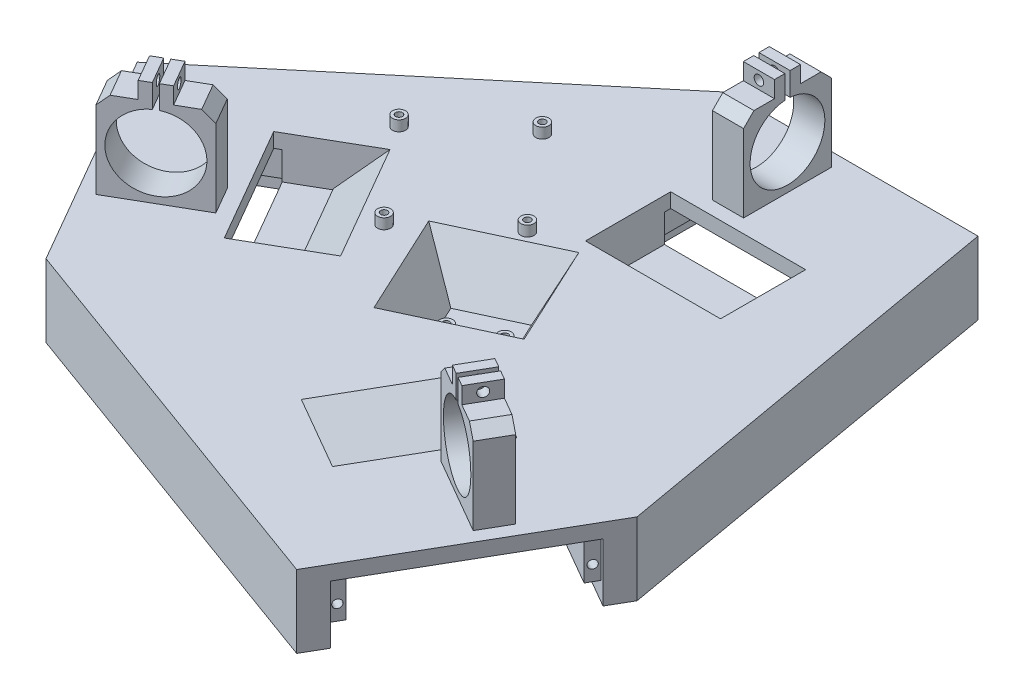
SolidWorks part; units mm, degrees
note: '?' marks a value the reader was unsure of.
ref_plane "Front Plane" through (0, 0, 0) normal (0, 0, 1) x (1, 0, 0)
ref_plane "Top Plane" through (0, 0, 0) normal (0, 1, 0) x (1, 0, 0)
ref_plane "Right Plane" through (0, 0, 0) normal (1, 0, 0) x (0, 0, -1)
sketch "Sketch1" plane through (0, 0, 0) normal (0, 1, 0) x (1, 0, 0)
  line L3 (-125, -72.1688) -> (0, 0)
  line L4 (0, 0) -> (125, -72.1688)
  line L5 (0, 144.3376) -> (0, 0)
  line L6 (-20, 144.3376) -> (100, 144.3376)
  line L7 (135, -54.8483) -> (75, -158.7713)
  line L8 (-175, 14.4338) -> (-115, -89.4893)
  line L9 (-175, 14.4338) -> (-20, 144.3376)
  line L10 (100, 144.3376) -> (135, -54.8483)
  line L11 (75, -158.7713) -> (-115, -89.4893)
  line L12 (0, 0) -> (129.9038, -75) construction
  dimension "D1" = 250
  dimension "D2" = 120
  dimension "D3" = 120
  dimension "D4" = 120
  dimension "D5" = 100
  dimension "D6" = 100
  dimension "D7" = 100
extrude "Boss-Extrude1" add sketch "Sketch1" along normal blind 35
ref_axis "Central Axis" through (0, -4.265, 0) along (0, 1, 0)?
ref_plane "Mechanism Arm Plane" through (0, 0, 0) normal (1, 0, 0) x (0, 0, -1)
ref_plane "Mech Arm Plane 2" through (0, 0, 0) normal (0.5, 0, 0.866) x (0, 1, 0)
ref_plane "Mech Arm Plane 3" through (0, 0, 0) normal (0.5, 0, -0.866) x (0, 1, 0)
ref_plane "Camera Plane" through (0, 10, 0) normal (0, 1, 0) x (1, 0, 0)
sketch "Sketch16" plane through (0, 10, 0) normal (0, 1, 0) x (1, 0, 0)
  line L0 (-7.5666, -8.8618) -> (-16.5148, 10.3572)
  line L1 (-7.5666, -8.8618) -> (11.6524, 0.0863)
  line L2 (-16.5148, 10.3572) -> (2.7043, 19.3053)
  line L3 (11.6524, 0.0863) -> (2.7043, 19.3053)
  line L4 (-7.5666, -8.8618) -> (2.7043, 19.3053) construction
  line L5 (-16.5148, 10.3572) -> (11.6524, 0.0863) construction
  line L6 (-21.8293, 12.2952) -> (4.6422, 24.6199)
  line L7 (16.9669, -1.8516) -> (4.6422, 24.6199)
  line L8 (-9.5046, -14.1764) -> (16.9669, -1.8516)
  line L9 (-9.5046, -14.1764) -> (-21.8293, 12.2952)
  point P1 (-2.4312, 5.2218)
  dimension "D1" = 4
  dimension "D2" = 21.2
sketch "Sketch2" plane through (0, 0, -144.3376) normal (0, 0, -1) x (-1, 0, 0)
  line L0 (-75, 0) -> (115, 0) construction
  line L1 (-88, 0) -> (8, 0)
  line L2 (-88, 0) -> (-88, 28)
  line L3 (-88, 28) -> (8, 28)
  line L4 (8, 0) -> (8, 28)
  line L5 (-40, 28) -> (-40, 0) construction
  line L6 (20, 35) -> (20, 0) construction
  line L7 (-100, 35) -> (-100, 0) construction
  dimension "D1" = 28
  dimension "D2" = 96
extrude "Cut-Extrude1" cut sketch "Sketch2" against normal blind 2.5
sketch "Sketch3" plane through (0, 0, -141.8376) normal (0, 0, -1) x (-1, 0, 0)
  line L0 (8, 0) -> (8, 28) construction
  line L1 (-88, 0) -> (8, 0)
  line L2 (-88, 0) -> (-88, 9)
  line L3 (-88, 9) -> (8, 9)
  line L4 (8, 0) -> (8, 9)
  line L5 (8, 28) -> (-88, 28) construction
  line L6 (-82, 9) -> (2, 9)
  line L7 (-82, 9) -> (-82, 28)
  line L8 (-82, 28) -> (2, 28)
  line L9 (2, 9) -> (2, 28)
  line L10 (-40, 28) -> (-40, 9) construction
  line L11 (-88, 28) -> (-88, 0) construction
  line M6 (-88, 28) -> (-88, 0)
  line M7 (-88, 0) -> (8, 0)
  line M8 (8, 0) -> (8, 28)
  line M9 (8, 28) -> (-88, 28)
  dimension "D1" = 9
  dimension "D2" = 84
extrude "Cut-Extrude2" cut sketch "Sketch3" against normal blind 56 contours L10 L8 L7 L3 | L10 L6 L9 M9 | L3 L6 M6 M7 M8
sketch "Sketch4" plane through (0, 0, -141.8376) normal (0, 0, -1) x (-1, 0, 0)
  line L0 (-85, 9) -> (-85, 28) construction
  line L1 (-88, 9) -> (-82, 9) construction
  line L2 (8, 28) -> (-88, 28) construction
  line L3 (5, 9) -> (5, 28) construction
  line L4 (2, 9) -> (8, 9) construction
  circle A0 centre (-85, 16.25) radius 2
  circle A1 centre (5, 16.25) radius 2
  dimension "D1" = 4
  dimension "D2" = 7.25
extrude "Cut-Extrude3" cut sketch "Sketch4" against normal blind 6
sketch "Sketch5" plane through (0, 0, -85.8376) normal (0, 0, -1) x (-1, 0, 0)
  line L0 (-40, 36.5) -> (-40, 14.5) construction
  line L1 (-72.5, 14.5) -> (-7.5, 14.5)
  line L2 (-72.5, 14.5) -> (-72.5, 36.5)
  line L3 (-72.5, 36.5) -> (-7.5, 36.5)
  line L4 (-7.5, 14.5) -> (-7.5, 36.5)
  line L5 (2, 9) -> (2, 28) construction
  line L6 (-82, 9) -> (-82, 28) construction
  line L7 (2, 9) -> (8, 9) construction
  dimension "D1" = 22
  dimension "D2" = 65
  dimension "D3" = 5.5
extrude "Cut-Extrude4" cut sketch "Sketch5" against normal blind 18 and the other way blind 3
chamfer "Chamfer2" distance 20 angle 45 1 edges at (40, 35, -67.8376)
ref_plane "Plane2" through (36, 0, 0) normal (1, 0, 0) x (0, 0, -1)
sketch "Sketch7" plane through (36, 0, 0) normal (1, 0, 0) x (0, 0, -1)
  line L0 (144.3376, 35) -> (-54.8483, 35) construction
  line L1 (95.4376, 35) -> (137.7376, 35)
  line L2 (95.4376, 35) -> (95.4376, 72.3)
  line L3 (100.4376, 77.3) -> (115.3376, 77.3)
  line L4 (137.7376, 35) -> (137.7376, 72.3)
  line L5 (144.3376, 35) -> (144.3376, 0) construction
  line L6 (95.4376, 72.3) -> (100.4376, 77.3)
  line L7 (132.7376, 77.3) -> (137.7376, 72.3)
  line L8 (95.4376, 56.15) -> (137.7376, 56.15) construction
  line L9 (116.5876, 56.15) -> (116.5876, 35) construction
  line L10 (115.3376, 77.3) -> (115.3376, 74.1065)
  line L11 (117.8376, 77.3) -> (117.8376, 74.1065)
  line L12 (117.8376, 77.3) -> (132.7376, 77.3)
  line L13 (115.3376, 77.3) -> (115.3376, 85.3)
  line L14 (115.3376, 85.3) -> (110.3376, 85.3)
  line L15 (110.3376, 85.3) -> (110.3376, 77.3)
  line L16 (117.8376, 77.3) -> (117.8376, 85.3)
  line L17 (117.8376, 85.3) -> (122.8376, 85.3)
  line L18 (122.8376, 85.3) -> (122.8376, 77.3)
  arc A0 (115.3376, 74.1065) -> (117.8376, 74.1065) centre (116.5876, 56.15) ccw
  point P1 (137.7376, 77.3)
  point P2 (95.4376, 77.3)
  point P22 (116.5876, 35)
  dimension "D4" = 36
  dimension "D1" = 42.3
  dimension "D2" = 6.6
  dimension "D3" = 42.3
  dimension "D5" = 2.5
  dimension "D8" = 5
  dimension "D9" = 8
extrude "Boss-Extrude4" add sketch "Sketch7" against normal blind 15 contours L14 L15 L3 L13 | L18 L17 L16 L12
sketch "Sketch10" plane through (0, 0, -122.8376) normal (0, 0, -1) x (-1, 0, 0)
  line L0 (-36, 81.3) -> (-21, 81.3) construction
  line L1 (-36, 85.3) -> (-36, 77.3) construction
  line L2 (-21, 85.3) -> (-21, 77.3) construction
  line L3 (-28.5, 85.3) -> (-28.5, 77.3) construction
  line L4 (-21, 85.3) -> (-36, 85.3) construction
  line L5 (-21, 77.3) -> (-36, 77.3) construction
  circle A0 centre (-28.5, 81.3) radius 2.3
  dimension "D1" = 4.6
extrude "Cut-Extrude5" cut sketch "Sketch10" against normal up to surface (12.5 mm away) up to face at (28.5, 81.3, -110.3376)
pattern_circular "Motor/Driver Patterned" count 3 over 360 about axis through (0, 0, 0) along (0, 1, 0) of "Cut-Extrude4", "Cut-Extrude3", "Cut-Extrude2", "Cut-Extrude1", "Cut-Extrude5", "Boss-Extrude4", "Chamfer2"
extrude "Cut-Extrude6" cut sketch "Sketch16" along normal up to surface (25 mm away) draft 26.75 contours L9 L8 L7 L6 L3 L1 L0 L2 | L1 L3 L2 L0
sketch "Sketch11" plane through (0, 35, 0) normal (0, 1, 0) x (1, 0, 0)
  line L0 (-85.1107, 50.6262) -> (-47.5559, 82.1005) construction
  line L1 (-85.1107, 50.6262) -> (-47.8554, 6.1735) construction
  line L2 (-47.5559, 82.1005) -> (-10.3006, 37.6479) construction
  line L3 (-47.8554, 6.1735) -> (-10.3006, 37.6479) construction
  line L4 (-47.5559, 82.1005) -> (-47.8554, 6.1735) construction
  line L5 (-175, 14.4338) -> (-20, 144.3376) construction
  circle A0 centre (-10.3006, 37.6479) radius 1.65
  circle A1 centre (-47.8554, 6.1735) radius 1.65
  circle A2 centre (-85.1107, 50.6262) radius 1.65
  circle A3 centre (-47.5559, 82.1005) radius 1.65
  circle A4 centre (-10.3006, 37.6479) radius 3.15
  circle A5 centre (-47.5559, 82.1005) radius 3.15
  circle A6 centre (-85.1107, 50.6262) radius 3.15
  circle A7 centre (-47.8554, 6.1735) radius 3.15
  dimension "D3" = 3.3
  dimension "D1" = 58
  dimension "D2" = 49
  dimension "D5" = 30
  dimension "D4" = 1.5
extrude "RaspberryPi5 Standoff" add sketch "Sketch11" along normal blind 5
sketch "Sketch13" plane through (0, 10, 0) normal (0, 1, 0) x (1, 0, 0)
  line L0 (-7.5666, -8.8618) -> (-11.6524, -0.0863) construction
  line L1 (-7.5666, -8.8618) -> (11.6524, 0.0863) construction
  line L2 (-11.6524, -0.0863) -> (7.5666, 8.8618) construction
  line L3 (11.6524, 0.0863) -> (7.5666, 8.8618) construction
  line L4 (-7.5666, -8.8618) -> (7.5666, 8.8618) construction
  line L5 (-11.6524, -0.0863) -> (11.6524, 0.0863) construction
  line L6 (-47.8554, 6.1735) -> (-10.3006, 37.6479) construction
  circle A0 centre (-11.6524, -0.0863) radius 1.65
  circle A1 centre (7.5666, 8.8618) radius 1.65
  circle A2 centre (11.6524, 0.0863) radius 1.65
  circle A3 centre (-7.5666, -8.8618) radius 1.65
  circle A4 centre (-10.3006, 37.6479) radius 1.65 construction
  circle A5 centre (7.5666, 8.8618) radius 3.15
  circle A6 centre (-11.6524, -0.0863) radius 3.15
  circle A7 centre (-7.5666, -8.8618) radius 3.15
  circle A8 centre (11.6524, 0.0863) radius 3.15
  circle A9 centre (-10.3006, 37.6479) radius 3.15 construction
  point P1 (0, 0)
  dimension "D1" = 9.68
  dimension "D2" = 21.2
  dimension "D3" = 15
extrude "Boss-Extrude6" add sketch "Sketch13" along normal blind 5
sketch "Sketch12" [suppressed] plane through (0, 35, 0) normal (0, 1, 0) x (1, 0, 0)
  line L0 (0, 0) -> (-35.4629, 28.8743)
  line L2 (0, 0) -> (-7.2744, -45.1489)
  line L3 (75, -158.7713) -> (-115, -89.4893) construction
  line L4 (-35.4629, 28.8743) -> (-22.8351, 44.3836)
  line L6 (-7.2744, -45.1489) -> (-27.0198, -41.9675)
  line L7 (-27.0198, -41.9675) -> (-34.9733, -91.3309)
  line L8 (-34.9733, -91.3309) -> (-15.2279, -94.5123)
  line L9 (-15.2279, -94.5123) -> (-20, -124.1303)
  line L10 (-22.8351, 44.3836) -> (-61.6082, 75.9532)
  line L11 (-61.6082, 75.9532) -> (-74.2361, 60.4439)
  line L12 (-74.2361, 60.4439) -> (-97.5, 79.3857)
  line L13 (0, 0) -> (42.7373, 16.2746)
  line L14 (42.7373, 16.2746) -> (49.8548, -2.4161)
  line L15 (49.8548, -2.4161) -> (96.5815, 15.3777)
  line L16 (96.5815, 15.3777) -> (89.464, 34.0684)
  line L17 (89.464, 34.0684) -> (117.5, 44.7446)
  point P22 (0, 0)
  dimension "D1" = 50
  dimension "D2" = 20
  dimension "D3" = 30
  dimension "D4" = 3
extrude "Thirds Split" [suppressed] cut sketch "Sketch12" against normal through all both and the other way through all thin contours L2 L6 L7 L8 L9 | L0 L4 L10 L11 L12 | L13 L14 L15 L16 L17
